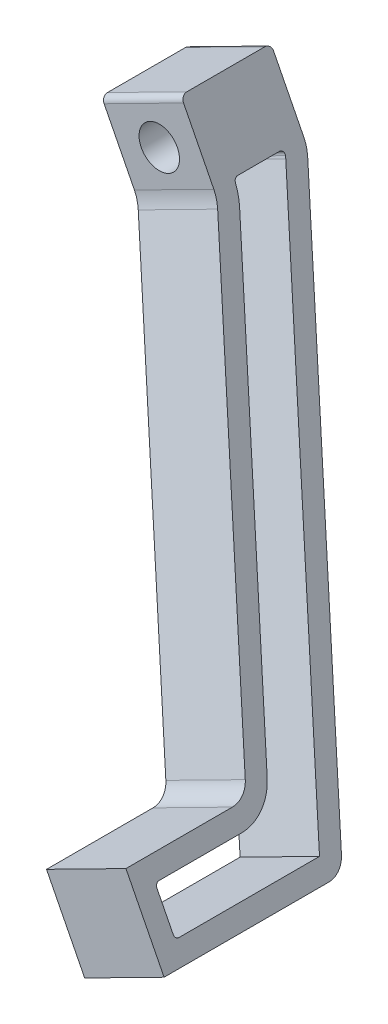
SolidWorks part; units mm, degrees
ref_plane "Front Plane" through (0, 0, 0) normal (0, 0, 1) x (1, 0, 0)
ref_plane "Top Plane" through (0, 0, 0) normal (0, 1, 0) x (1, 0, 0)
ref_plane "Right Plane" through (0, 0, 0) normal (1, 0, 0) x (0, 0, -1)
ref_plane "Plane1" through (627.0375, 0, 0) normal (-1, 0, 0) x (0, 0, 1)
ref_plane "Plane2" through (0, 845.4923, 0) normal (0, 1, 0) x (1, 0, 0)
ref_axis "Axis1" through (627.0375, 845.4923, 1293.2699) along (0, 0, 1)
ref_plane "Plane3" through (839.8175, 426.9856, 0) normal (-0.8914, -0.4532, 0) x (0, 0, 1)
sketch "Sketch2" plane through (0, 0, 1293.5874) normal (0, 0, -1) x (-1, 0, 0)
  line L0 (-627.0375, 863.4923) -> (-627.0375, 827.4923) construction
  line L1 (-646.0375, 863.4923) -> (-608.0375, 863.4923) construction
  line L2 (-608.0375, 827.4923) -> (-646.0375, 827.4923) construction
  point P6 (-627.0375, 845.4923)
sketch "Sketch3" plane through (0, 0, 1293.5874) normal (0, 0, -1) x (-1, 0, 0)
  line L0 (-617.4102, 863.4923) -> (-636.6648, 827.4923) construction
  line L1 (-608.0375, 827.4923) -> (-646.0375, 827.4923) construction
  line L2 (-633.8616, 832.7333) -> (-624.0627, 827.4923) construction
  line L3 (-620.2133, 858.2513) -> (-630.0123, 863.4923) construction
  line L4 (-646.0375, 863.4923) -> (-608.0375, 863.4923) construction
  line L5 (-627.0375, 863.4923) -> (-627.0375, 827.4923) construction
  line L6 (-630.0123, 863.4923) -> (-643.6606, 837.9742) construction
  line L7 (-643.6606, 837.9742) -> (-633.8616, 832.7333) construction
  line L8 (-620.2133, 858.2513) -> (-610.4144, 853.0104) construction
  line L9 (-610.4144, 853.0104) -> (-624.0627, 827.4923) construction
  line L10 (-641.884, 841.296) -> (-622.286, 830.8141) construction
  line L11 (-637.2028, 838.7923) -> (-640.0375, 833.4923) construction
  line L12 (-631.789, 860.1706) -> (-612.191, 849.6886) construction
  line L13 (-614.0375, 857.4923) -> (-616.8722, 852.1923) construction
  line L14 (-634.7375, 854.6576) -> (-640.0375, 857.4923) construction
  point P6 (-627.0375, 845.4923)
  point P22 (-632.085, 836.055)
  point P28 (-621.99, 854.9296)
  dimension "D1" = 22.225
  dimension "D2" = 28.14
sketch "Sketch4" plane through (839.8547, 426.9124, 0) normal (0.8914, 0.4532, 0) x (0, 0, -1)
  line L0 (-1203.4253, 589.2353) -> (-1225.8915, 589.2353) construction
  line L1 (-1293.5874, 459.0746) -> (-1293.5874, 480.0746)
  line L2 (-1214.6584, 589.2353) -> (-1214.6584, 579.2353) construction
  line L3 (-1256.3458, 469.5746) -> (-1293.5874, 469.5746) construction
  line L4 (-1203.4253, 599.2353) -> (-1203.4253, 579.2353)
  line L5 (-1214.6584, 579.2353) -> (-1256.3458, 469.5746) construction
  line L6 (-1203.4253, 599.2353) -> (-1225.8915, 599.2353)
  line L7 (-1225.8915, 599.2353) -> (-1225.8915, 579.2353)
  line L8 (-1225.8915, 579.2353) -> (-1263.5874, 480.0746)
  line L9 (-1203.4253, 579.2353) -> (-1225.8915, 579.2353) construction
  line L10 (-1203.4253, 579.2353) -> (-1249.1043, 459.0746)
  line L14 (-1293.5874, 480.0746) -> (-1263.5874, 480.0746)
  line L15 (-1293.5874, 459.0746) -> (-1249.1043, 459.0746)
  point P5 (-1214.6584, 589.2353)
  point P10 (-1293.5874, 469.5746)
  point P14 (-1203.4253, 589.2353)
  point P20 (-1214.6584, 579.2353)
  dimension "D1" = 21
  dimension "D2" = 20
  dimension "D3" = 90.1621
  dimension "D4" = 30
  dimension "D5" = 21
  dimension "D6" = 119.6607
extrude "Boss-Extrude1" add sketch "Sketch4" along normal mid plane 22.225
sketch "Sketch5" plane through (0, 0, 1203.4253) normal (0, 0, -1) x (-1, 0, 0)
  line L0 (-578.1793, 966.1085) -> (-567.4322, 938.2078) construction
  point P4 (-572.8057, 952.1581)
hole_wizard "3/8 Clearance Hole1" positions "Sketch8" profile "Sketch7" hole size "3/8" standard "ANSI Inch" end condition through all
sketch "Sketch8" plane through (0, 0, 1203.4253) normal (0, 0, -1) x (-1, 0, 0)
  point P0 (-572.8057, 952.1581)
sketch "Sketch7" plane through (572.8057, 952.1581, 1203.4253) normal (1, 0, 0) x (0, 1, 0)
  line L0 (0, 0) -> (0, 90.1621)
  line L1 (0, 90.1621) -> (5.0419, 90.1621)
  line L2 (5.0419, 90.1621) -> (5.0419, 0)
  line L5 (5.0419, 0) -> (0, 0)
  line L11 (0, -6.35) -> (0, 107.95) construction
  dimension "Thru Hole Dia." = 10.0838
  dimension "Thru Hole Depth" = 90.1621
fillet "Fillet1" radius 10 2 edges at (577.3379, 943.2441, 1225.8915) (577.3379, 943.2441, 1203.4253)
fillet "Fillet2" radius 5 2 edges at (631.7962, 836.1326, 1249.1043) (622.2788, 854.852, 1263.5874)
fillet "Fillet3" radius 1.5 2 edges at (568.2736, 961.0721, 1203.4253) (568.2736, 961.0721, 1225.8915)
sketch "Sketch9" plane through (849.7232, 432.022, 0) normal (0.8914, 0.4532, 0) x (0, 0, -1)
  line L0 (-1220.8915, 580.9897) -> (-1208.4253, 580.9897)
  line L9 (-1267.0357, 474.9924) -> (-1288.5874, 474.9924)
  line L10 (-1267.0357, 474.9924) -> (-1288.5874, 474.9924)
  line L11 (-1288.5874, 463.9924) -> (-1252.5527, 463.9924)
  line L12 (-1288.5874, 463.9924) -> (-1252.5527, 463.9924)
  line L16 (-1208.4253, 580.9897) -> (-1208.4253, 594.1531)
  line L17 (-1208.4253, 594.1531) -> (-1220.8915, 594.1531)
  line L18 (-1220.8915, 594.1531) -> (-1220.8915, 580.9897)
  line L19 (-1221.8705, 575.6597) -> (-1257.6884, 481.439)
  line L21 (-1288.5874, 474.9924) -> (-1288.5874, 463.9924)
  line L23 (-1252.5527, 463.9924) -> (-1208.7516, 579.213)
  line L27 (-1221.8705, 575.6597) -> (-1257.6884, 481.439)
  line L29 (-1288.5874, 474.9924) -> (-1288.5874, 463.9924)
  line L31 (-1252.5527, 463.9924) -> (-1208.7516, 579.213)
  arc A6 (-1267.0357, 474.9924) -> (-1257.6884, 481.439) centre (-1267.0357, 484.9924) ccw
  arc A7 (-1267.0357, 474.9924) -> (-1257.6884, 481.439) centre (-1267.0357, 484.9924) ccw
  arc A12 (-1221.8705, 575.6597) -> (-1220.8915, 580.9897) centre (-1235.8915, 580.9897) ccw
  arc A15 (-1208.7516, 579.213) -> (-1208.4253, 580.9897) centre (-1213.4253, 580.9897) ccw
  arc A16 (-1221.8705, 575.6597) -> (-1220.8915, 580.9897) centre (-1235.8915, 580.9897) ccw
  arc A19 (-1208.7516, 579.213) -> (-1208.4253, 580.9897) centre (-1213.4253, 580.9897) ccw
  dimension "D1" = 5
extrude "Cut-Extrude1" cut sketch "Sketch9" against normal up to next
fillet "Fillet4" radius 1 4 edges at (576.5055, 944.8813, 1208.4253) (576.5055, 944.8813, 1220.8915) (629.5302, 840.5896, 1288.5874) (624.5448, 850.395, 1288.5874)
equation "\"Steering_Arm_Thickness\"= 1in"
